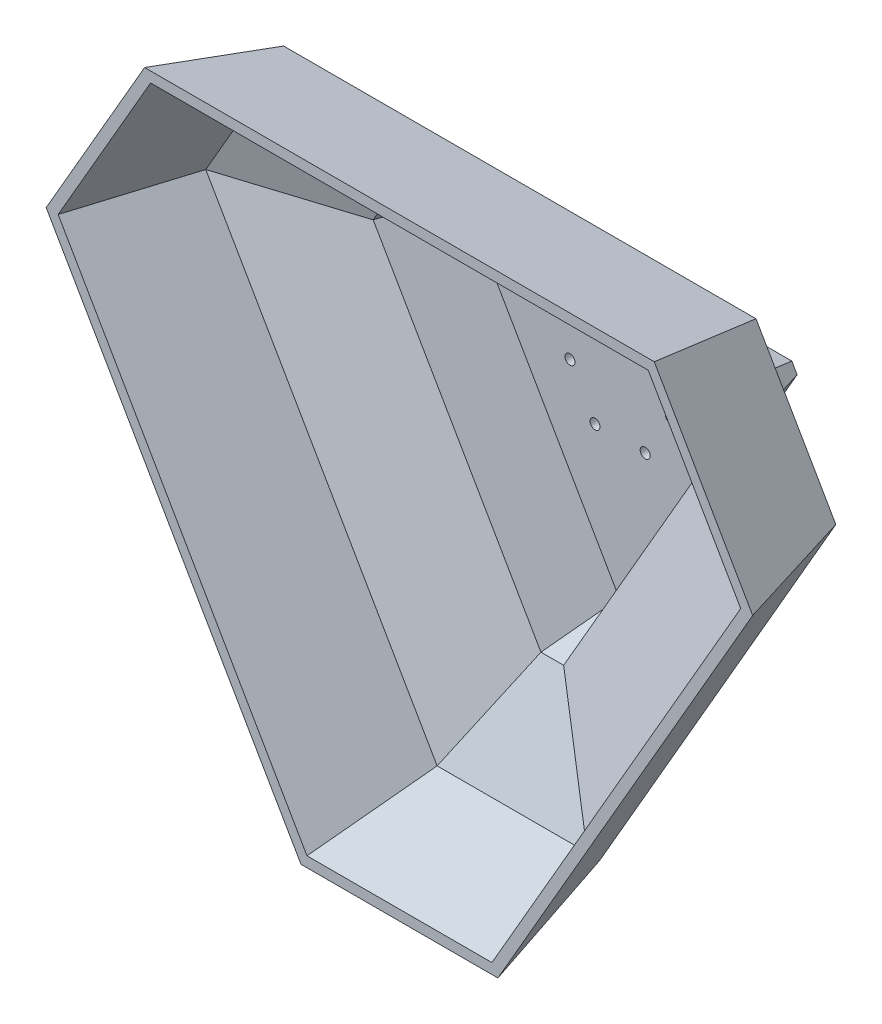
SolidWorks part; units mm, degrees
material "ABS"
ref_plane "Front Plane" through (0, 0, 0) normal (0, 0, 1) x (1, 0, 0)
ref_plane "Top Plane" through (0, 0, 0) normal (0, 1, 0) x (1, 0, 0)
ref_plane "Right Plane" through (0, 0, 0) normal (1, 0, 0) x (0, 0, -1)
sketch "Sketch1" plane through (0, 0, 0) normal (0, 0, 1) x (1, 0, 0)
  line L0 (0, 0) -> (0, 130) construction
  line L1 (127.0171, 130) -> (-127.0171, 130)
  line L2 (-176.0918, 45) -> (-49.0748, -175)
  line L3 (49.0748, -175) -> (176.0918, 45)
  line L4 (0, 0) -> (151.5544, 87.5) construction
  line L5 (0, 0) -> (-151.5544, 87.5) construction
  line L6 (0, 0) -> (0, -175) construction
  line L7 (-176.0918, 45) -> (-127.0171, 130)
  line L8 (127.0171, 130) -> (176.0918, 45)
  line L9 (-49.0748, -175) -> (49.0748, -175)
  circle A0 centre (0, 0) radius 130 construction
  point P8 (0, 130)
  dimension "D1" = 305
  dimension "D2" = 175
extrude "Boss-Extrude1" add sketch "Sketch1" against normal blind 60 draft 15
sketch "Sketch4" plane through (0, 0, -60) normal (0, 0, -1) x (-1, 0, 0)
  line L0 (39.7927, -158.923) -> (-39.7927, -158.923)
  line L1 (-39.7927, -158.923) -> (-157.5278, 45)
  line L2 (-157.5278, 45) -> (-117.735, 113.923)
  line L3 (-117.735, 113.923) -> (117.735, 113.923)
  line L4 (117.735, 113.923) -> (157.5278, 45)
  line L5 (157.5278, 45) -> (39.7927, -158.923)
extrude "Boss-Extrude4" add sketch "Sketch4" along normal blind 20 draft 70
sketch "Sketch5" plane through (0, 0, -80) normal (0, 0, -1) x (-1, 0, 0)
  line L0 (8.0676, -103.9735) -> (-8.0676, -103.9735)
  line L1 (-8.0676, -103.9735) -> (-94.0775, 45)
  line L2 (-94.0775, 45) -> (-86.0099, 58.9735)
  line L3 (-86.0099, 58.9735) -> (86.0099, 58.9735)
  line L4 (86.0099, 58.9735) -> (94.0775, 45)
  line L5 (94.0775, 45) -> (8.0676, -103.9735)
extrude "Boss-Extrude5" add sketch "Sketch5" along normal blind 35 draft 15
shell "Shell2" thickness 5 removed face at (0, 0, 0)
sketch "Sketch6" plane through (0, 0, -115) normal (0, 0, -1) x (-1, 0, 0)
  line L0 (0, 0) -> (0, 21.6506) construction
  line L7 (12.5, 21.6506) -> (-12.5, 21.6506) construction
  line L8 (-12.5, 21.6506) -> (-25, 0) construction
  line L9 (-25, 0) -> (-12.5, -21.6506) construction
  line L10 (-12.5, -21.6506) -> (12.5, -21.6506) construction
  line L11 (12.5, -21.6506) -> (25, 0) construction
  line L12 (25, 0) -> (12.5, 21.6506) construction
  line L13 (0, 0) -> (-25, 0) construction
  circle A0 centre (0, 0) radius 32.5
  circle A1 centre (0, 0) radius 31.5
  circle A2 centre (0, 0) radius 15.75
  circle A3 centre (0, 0) radius 21.6506 construction
  circle A10 centre (-12.5, 21.6506) radius 2.5
  circle A11 centre (-25, 0) radius 2.5
  circle A12 centre (-12.5, -21.6506) radius 2.5
  circle A13 centre (12.5, -21.6506) radius 2.5
  circle A14 centre (25, 0) radius 2.5
  circle A15 centre (12.5, 21.6506) radius 2.5
  point P13 (0, 21.6506)
  dimension "D2" = 5
  dimension "D3" = 31.5
  dimension "D4" = 63
  dimension "D5" = 65
  dimension "D1" = 25
extrude "Boss-Extrude6" add sketch "Sketch6" along normal blind 7 contours A0 A1 region at (31.5808, 0, -115)
extrude "Boss-Extrude7" add sketch "Sketch6<3>" along normal blind 7 draft 10 contours A2 region at (0, 0, -115)
sketch "Sketch6<3>" plane through (0, 0, -115) normal (0, 0, -1) x (-1, 0, 0) same geometry as "Sketch6"
extrude "Cut-Extrude1" cut sketch "Sketch6<4>" against normal up to next contours A11 | A10 | A15 | A14 | A13 | A12 region at (12.5, 21.6506, -115) region at (25, 0, -115) region at (12.5, -21.6506, -115) region at (-12.5, -21.6506, -115) region at (-25, 0, -115) region at (-12.5, 21.6506, -115)
sketch "Sketch6<4>" plane through (0, 0, -115) normal (0, 0, -1) x (-1, 0, 0) same geometry as "Sketch6"
fillet "Fillet1" radius 10 1 edges at (32.5, 0, -115)
ref_axis "Axis1" [suppressed] through (0, 0, -115) along (0, 0, -1)
